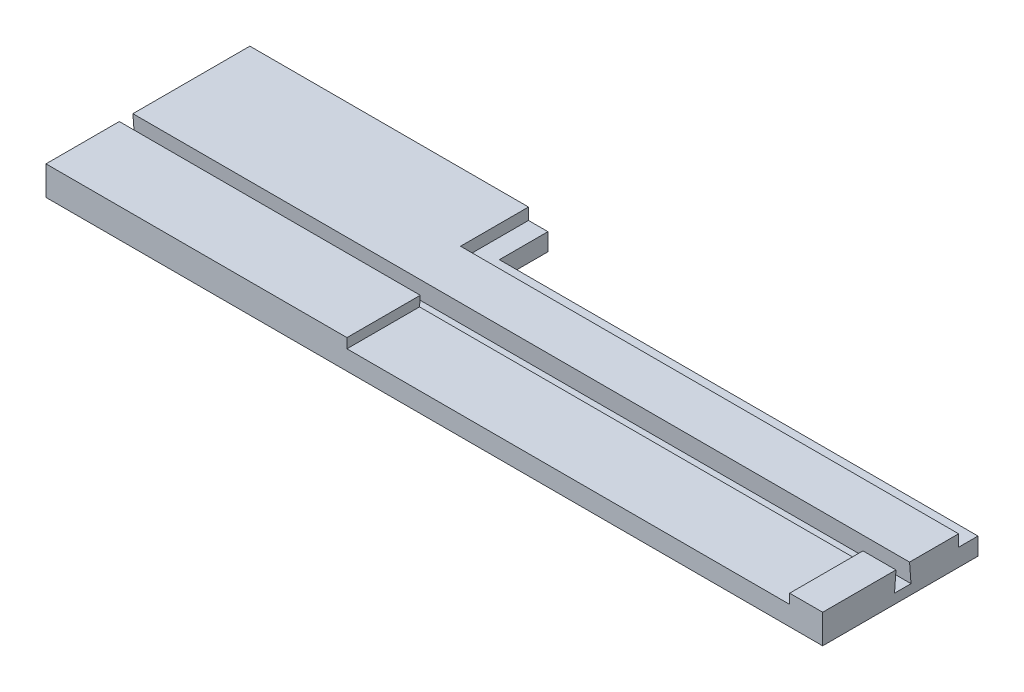
SolidWorks part; units mm, degrees
ref_plane "Front Plane" through (0, 0, 0) normal (0, 0, 1) x (1, 0, 0)
ref_plane "Top Plane" through (0, 0, 0) normal (0, 1, 0) x (1, 0, 0)
ref_plane "Right Plane" through (0, 0, 0) normal (1, 0, 0) x (0, 0, -1)
sketch "Sketch1" plane through (0, 0, 0) normal (0, 1, 0) x (1, 0, 0)
  line L1 (-7.5455, 9.1364) -> (72.4545, 9.1364)
  line L2 (-7.5455, 9.1364) -> (-7.5455, -4.8636)
  line L3 (-7.5455, -4.8636) -> (72.4545, -4.8636)
  line L4 (72.4545, 9.1364) -> (72.4545, -4.8636)
  dimension "D1" = 14
  dimension "D2" = 80
extrude "Boss-Extrude1" add sketch "Sketch1" along normal blind 2
sketch "Sketch2" plane through (0, 2, 0) normal (0, 1, 0) x (1, 0, 0)
  line L0 (72.4545, -4.8636) -> (72.4545, 9.1364) construction
  line L1 (-7.5455, -4.8636) -> (72.4545, -4.8636)
  line L2 (-7.5455, -4.8636) -> (-7.5455, 2.5364)
  line L3 (-7.5455, 2.5364) -> (72.4545, 2.5364)
  line L4 (72.4545, -4.8636) -> (72.4545, 2.5364)
  line L7 (-7.5455, 9.1364) -> (72.4545, 9.1364)
  line L8 (-7.5455, 9.1364) -> (-7.5455, 4.2364)
  line L9 (-7.5455, 4.2364) -> (72.4545, 4.2364)
  line L10 (72.4545, 9.1364) -> (72.4545, 4.2364)
  dimension "D1" = 7.4
  dimension "D2" = 1.7
  dimension "D3" = 4.9
extrude "Boss-Extrude2" add sketch "Sketch2" along normal blind 2 contours L3 L4 L1 L2 | L8 L9 L10 L7
sketch "Sketch3" plane through (0, 0, 0) normal (0, -1, 0) x (1, 0, 0)
  line L0 (72.4545, 4.8636) -> (72.4545, -9.1364) construction
  line L1 (-7.5455, -9.1364) -> (21.1545, -9.1364)
  line L2 (-7.5455, -9.1364) -> (-7.5455, -16.1364)
  line L3 (-7.5455, -16.1364) -> (21.1545, -16.1364)
  line L4 (21.1545, -9.1364) -> (21.1545, -16.1364)
  dimension "D1" = 7
  dimension "D2" = 51.3
extrude "Boss-Extrude3" add sketch "Sketch3" against normal up to surface (4 mm away) up to face at (32.4545, 4, -6.6864)
sketch "Sketch4" plane through (-7.5455, 0, 0) normal (-1, 0, 0) x (0, 0, 1)
  line L0 (-4.2364, 4) -> (-2.5364, 4) construction
  line L1 (-2.5364, 2) -> (-2.6864, 4)
  line L2 (-2.6864, 4) -> (-2.5364, 4)
  line L3 (-2.5364, 4) -> (-2.5364, 2)
  line L4 (-4.2364, 2) -> (-4.2364, 4)
  line L5 (-4.2364, 4) -> (-4.0864, 4)
  line L6 (-4.0864, 4) -> (-4.2364, 2)
  dimension "D1" = 0.15
  dimension "D2" = 0.15
extrude "Boss-Extrude4" add sketch "Sketch4" against normal up to surface (80 mm away) up to face at (72.4545, 2.5, -2.7614)
sketch "Sketch5" plane through (0, 0, 0) normal (0, -1, 0) x (1, 0, 0)
  line L0 (-7.5455, 4.8636) -> (72.4545, 4.8636)
  line L1 (72.4545, 4.8636) -> (72.4545, -9.1364)
  line L2 (72.4545, -9.1364) -> (21.1545, -9.1364)
  line L3 (21.1545, -9.1364) -> (21.1545, -16.1364)
  line L4 (21.1545, -16.1364) -> (-7.5455, -16.1364)
  line L5 (-7.5455, -16.1364) -> (-7.5455, 4.8636)
extrude "Cut-Extrude1" cut sketch "Sketch5" against normal blind 1
sketch "Sketch6" plane through (0, 1, 0) normal (0, -1, 0) x (1, 0, 0)
  line L1 (21.1545, -9.1364) -> (72.4545, -9.1364)
  line L2 (21.1545, -9.1364) -> (21.1545, -11.1364)
  line L3 (23.1545, -11.1364) -> (72.4545, -11.1364)
  line L4 (72.4545, -9.1364) -> (72.4545, -11.1364)
  line L5 (21.1545, -16.1364) -> (23.1545, -16.1364)
  line L6 (21.1545, -16.1364) -> (21.1545, -11.1364)
  line L8 (23.1545, -16.1364) -> (23.1545, -11.1364)
  line L9 (72.4545, -9.1364) -> (72.4545, 4.8636) construction
  dimension "D1" = 2
  dimension "D2" = 2
  dimension "D3" = 0
extrude "Boss-Extrude5" add sketch "Sketch6" against normal blind 1.8
sketch "Sketch7" plane through (0, 4, 0) normal (0, 1, 0) x (1, 0, 0)
  line L0 (-7.5455, -4.8636) -> (72.4545, -4.8636) construction
  line L1 (69.0545, -4.8636) -> (23.4545, -4.8636)
  line L2 (69.0545, -4.8636) -> (69.0545, 2.6864)
  line L3 (69.0545, 2.6864) -> (23.4545, 2.6864)
  line L4 (23.4545, -4.8636) -> (23.4545, 2.6864)
  line L5 (72.4545, 2.6864) -> (-7.5455, 2.6864) construction
  line L6 (72.4545, -4.8636) -> (72.4545, 2.6864) construction
  line L7 (-7.5455, -4.8636) -> (-7.5455, 2.6864) construction
  dimension "D1" = 3.4
  dimension "D2" = 31
extrude "Cut-Extrude2" cut sketch "Sketch7" against normal blind 1
